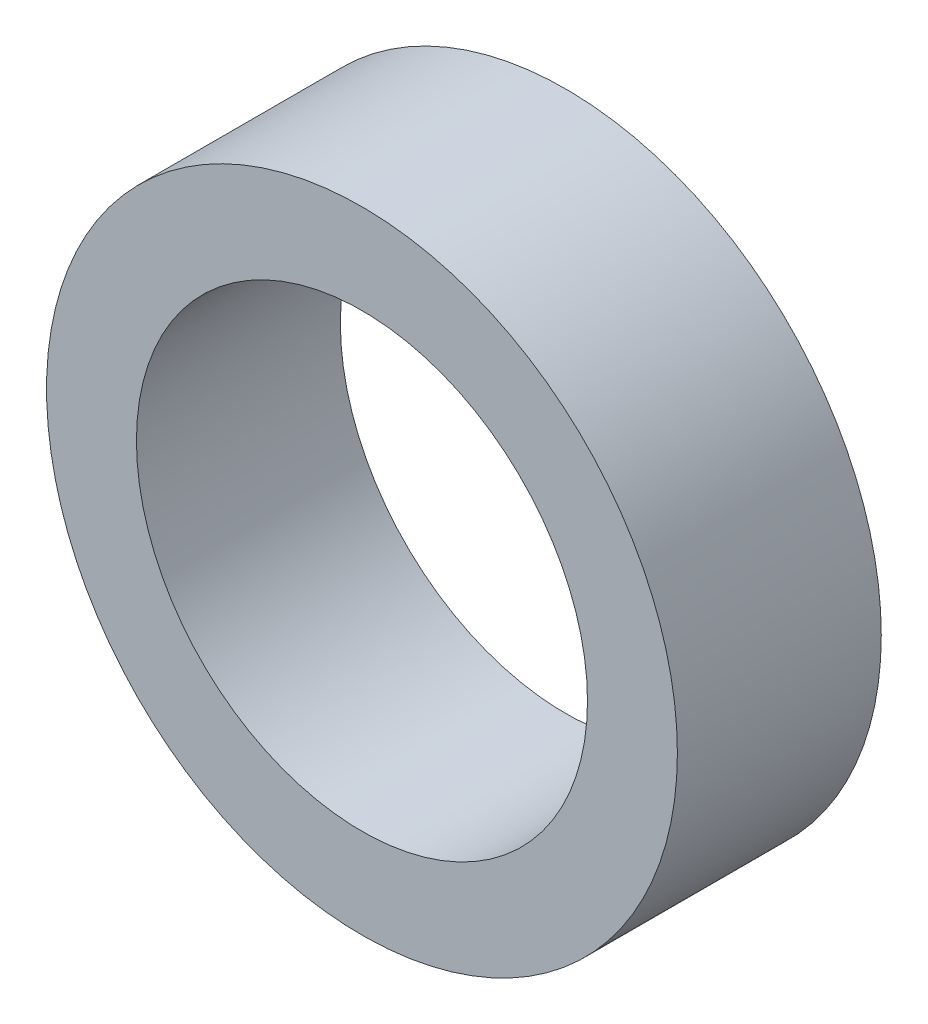
SolidWorks part; units mm, degrees
material "PET"
ref_plane "Front Plane" through (0, 0, 0) normal (0, 0, 1) x (1, 0, 0)
ref_plane "Top Plane" through (0, 0, 0) normal (0, 1, 0) x (1, 0, 0)
ref_plane "Right Plane" through (0, 0, 0) normal (1, 0, 0) x (0, 0, -1)
sketch "Sketch1" plane through (0, 0, 0) normal (0, 0, 1) x (1, 0, 0)
  circle A0 centre (0, 0) radius 3.9726
  circle A1 centre (0, 0) radius 5.5562
  dimension "D1" = 7.9451
  dimension "D2" = 11.1125
extrude "Boss-Extrude1" add sketch "Sketch1" along normal blind 3.5916
ref_axis "Axis1" through (0, 0, 3.5916) along (0, 0, -1)
